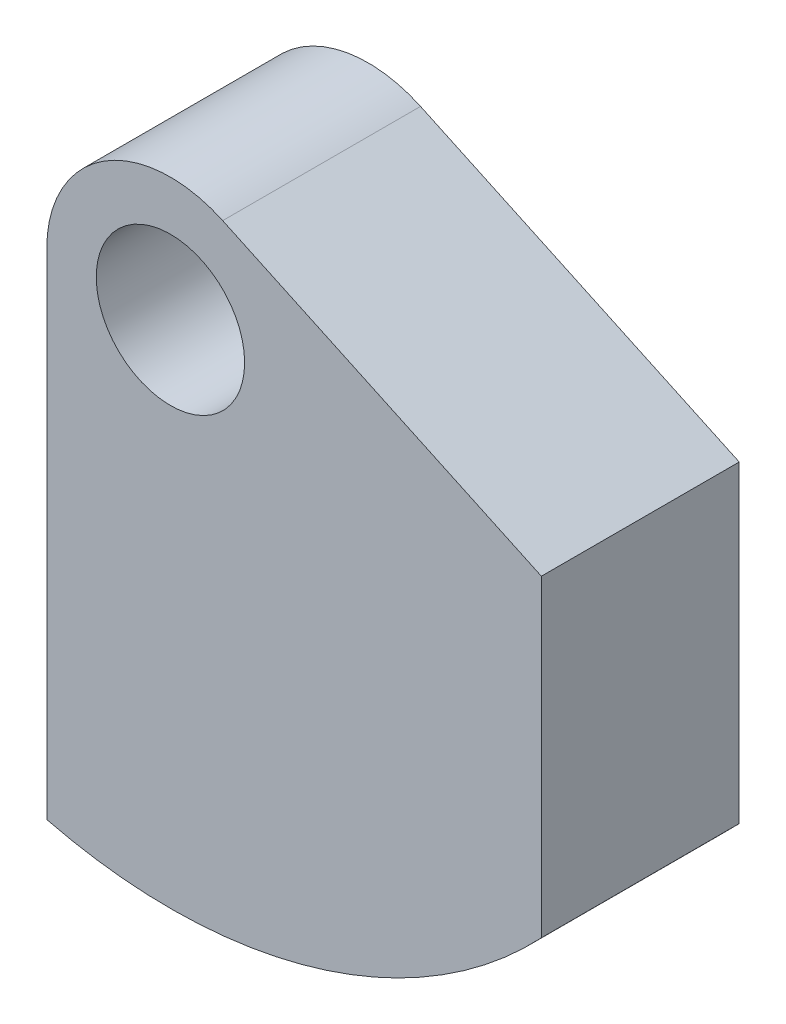
SolidWorks part; units mm, degrees
ref_plane "Спереди" through (0, 0, 0) normal (0, 0, 1) x (1, 0, 0)
ref_plane "Сверху" through (0, 0, 0) normal (0, 1, 0) x (1, 0, 0)
ref_plane "Справа" through (0, 0, 0) normal (1, 0, 0) x (0, 0, -1)
other "Configuration Table"
sketch "Эскиз1" plane through (0, 0, 0) normal (0, 0, 1) x (1, 0, 0)
  line L13 (-2.5, 0) -> (-2.5, -10)
  line L14 (1.0565, 2.2658) -> (10.1196, -1.9604)
  circle A1 centre (0, 0) radius 1.5
  circle A5 centre (0, 0) radius 2.5
  arc A7 (10.1196, -1.9604) -> (-2.5, -10) centre (0, 0) cw
  dimension "D3" = 5
  dimension "D1" = 65
  dimension "D2" = 3
  dimension "D7" = 10
extrude "Бобышка-Вытянуть1" add sketch "Эскиз1" along normal blind 4 contours A5 A1 | A7 L14 A5 L13 region at (3.122, -4.9005, 0) region at (-1.3053, 2.0488, 0)
sketch "Эскиз2" plane through (0, 0, 4) normal (0, 0, 1) x (1, 0, 0)
  line L0 (7.5, -0.7389) -> (7.5, -7.0711)
  line L1 (1.0565, 2.2658) -> (10.1196, -1.9604) construction
  line L2 (-2.5, 0) -> (-2.5, -10) construction
  line L3 (7.5, -0.7389) -> (10.1196, -1.9604)
  arc A0 (-2.5, -10) -> (10.1196, -1.9604) centre (0, 0) ccw construction
  arc A1 (7.5, -7.0711) -> (10.1196, -1.9604) centre (0, 0) ccw
  point P9 (7.5, -1.4434)
  point P13 (10.3066, -0.1529)
  point P14 (9.9181, -2.8073)
  point P15 (10.3024, -0.3332)
  dimension "D1" = 10
extrude "Вырез-Вытянуть1" cut sketch "Эскиз2" against normal through all
